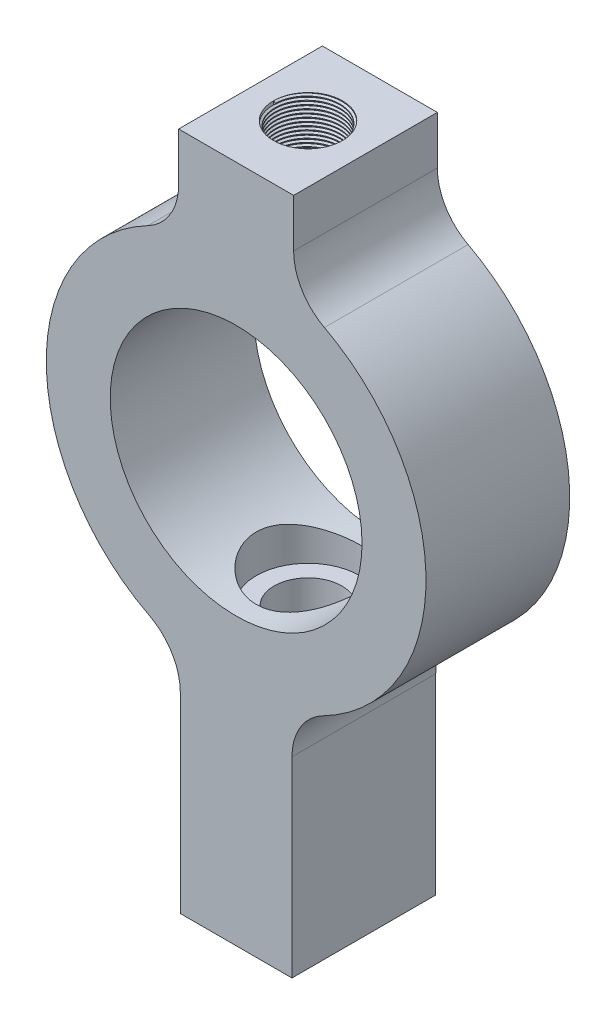
SolidWorks part; units mm, degrees
ref_plane "Front Plane" through (0, 0, 0) normal (0, 0, 1) x (1, 0, 0)
ref_plane "Top Plane" through (0, 0, 0) normal (0, 1, 0) x (1, 0, 0)
ref_plane "Right Plane" through (0, 0, 0) normal (1, 0, 0) x (0, 0, -1)
sketch "Sketch1" plane through (0, 0, 0) normal (0, 0, 1) x (1, 0, 0)
  line L4 (1.7715, -19.5604) -> (-7.9405, -19.5604)
  line L5 (-7.9405, -19.5604) -> (-7.9405, 0.4396)
  line L6 (1.7715, -19.5604) -> (1.7715, 0.4396)
  line L9 (1.9155, 39.4546) -> (-8.0845, 39.4546)
  line L13 (-8.0845, 39.4546) -> (-8.0845, 31.9546)
  line L14 (1.9155, 31.9546) -> (1.9155, 39.4546)
  arc A0 (1.7715, 0.4396) -> (1.9155, 31.9546) centre (-3.0845, 16.2196) ccw
  arc A1 (-8.0845, 31.9546) -> (-7.9405, 0.4396) centre (-3.0845, 16.2196) ccw
  circle A2 centre (-3.0845, 16.2196) radius 10.95
  point P8 (-3.0845, -19.5604)
extrude "Boss-Extrude1" add sketch "Sketch1" along normal blind 12.5
sketch "Sketch2" plane through (0, 39.4546, 0) normal (0, 1, 0) x (1, 0, 0)
  circle A0 centre (-3.0845, -6.25) radius 3
extrude "Cut-Extrude1" cut sketch "Sketch2" against normal blind 22
sketch "Sketch3" plane through (0, -19.5604, 0) normal (0, -1, 0) x (1, 0, 0)
  circle A0 centre (-3.0845, 6.25) radius 2.95
extrude "Cut-Extrude2" cut sketch "Sketch3" against normal blind 31
fillet "Fillet3" radius 5 2 edges at (1.9155, 31.9546, 6.25) (-8.0845, 31.9546, 6.25)
fillet "Fillet4" radius 5 1 edges at (-7.9405, 0.4396, 6.25)
fillet "Fillet5" radius 5 1 edges at (1.7715, 0.4396, 6.25)
ref_plane "Plane1" through (0, 2.9396, 0) normal (0, -1, 0) x (-1, 0, 0)
sketch "Sketch5" plane through (0, 2.9396, 0) normal (0, -1, 0) x (-1, 0, 0)
  circle A0 centre (3.0845, -6.25) radius 4.5
extrude "Cut-Extrude3" cut sketch "Sketch5" against normal blind 10
thread "Thread1" pitch 0.3175 method extrude profile "Thread Profile1" start angle 0, offset 0, length 10, pitch 0.3175, diameter 6
ref_plane "Plane2" through (-6.0845, 39.4546, 6.25) normal (0, 0, 1) x (-1, 0, 0)
sketch "Thread Profile1" plane through (-6.0845, 39.4546, 6.25) normal (0, 0, 1) x (-1, 0, 0)
  line L0 (0, 0) -> (0, 0.3175) construction
  line L11 (0, 0) -> (0, 0.2778)
  line L12 (0, 0.2778) -> (-0.1719, 0.1786)
  line L13 (-0.1719, 0.1786) -> (-0.1719, 0.0992)
  line L15 (-0.1719, 0.0992) -> (0, 0)
  line L17 (-0.1719, 0.1389) -> (0, 0.1389) construction
  point P2 (0, 0)
  dimension "Pitch" = 0.3175
  dimension "Profile_Angle" = 60
  dimension "Profile_Land" = 0.0794
  dimension "Profile_Height" = 0.1719
